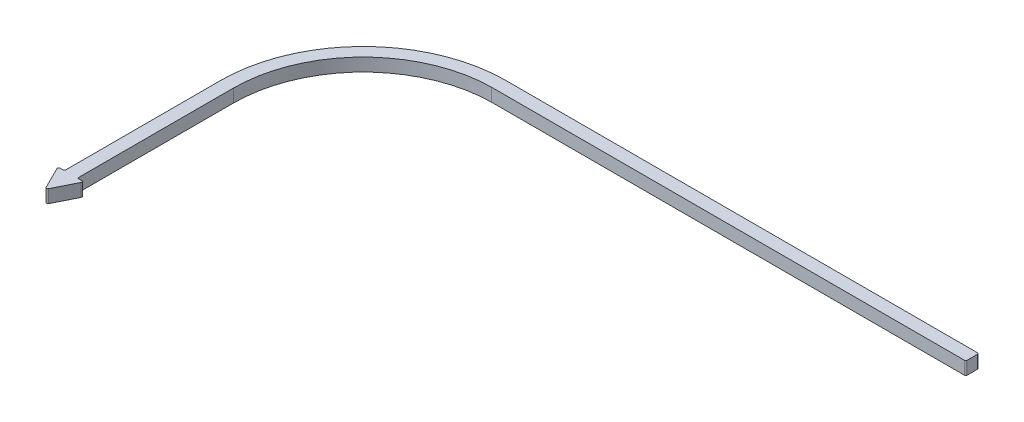
SolidWorks part; units mm, degrees
material "Acrylic (Medium-high impact)"
ref_plane "Front" through (0, 0, 0) normal (0, 0, 1) x (1, 0, 0)
ref_plane "Top" through (0, 0, 0) normal (0, 1, 0) x (1, 0, 0)
ref_plane "Right" through (0, 0, 0) normal (1, 0, 0) x (0, 0, -1)
sketch "Sketch1" plane through (0, 0, 0) normal (0, 1, 0) x (1, 0, 0)
  line L0 (69.0717, 158.7457) -> (69.0717, 152.3952)
  line L1 (0, 0) -> (6.35, 0)
  line L2 (0, 0) -> (0, 88.9)
  line L3 (0, 88.9) -> (6.35, 88.9)
  line L4 (6.35, 0) -> (6.35, 88.9)
  line L9 (69.0717, 158.7457) -> (300.8467, 158.7457)
  line L10 (69.0717, 152.3952) -> (300.8467, 152.3952)
  line L11 (300.8467, 158.7457) -> (300.8467, 152.3952)
  line L19 (9.525, 0) -> (-3.175, 0)
  line L20 (9.525, 0) -> (9.525, 12.7)
  line L21 (9.525, 12.7) -> (-3.175, 12.7)
  line L22 (-3.175, 0) -> (-3.175, 12.7)
  arc A0 (6.35, 88.9) -> (69.0717, 152.3952) centre (69.85, 88.9) cw
  arc A1 (0, 88.9) -> (69.0717, 158.7457) centre (69.85, 88.9) cw
  point P14 (3.175, 0)
  dimension "D1" = 6.35
  dimension "D2" = 88.9
  dimension "D3" = 231.775
  dimension "D4" = 63.5
  dimension "D5" = 12.7
  dimension "D6" = 12.7
  dimension "D7" = 12.7
  dimension "D8" = 6.35
extrude "Boss-Extrude1" add sketch "Sketch1" along normal blind 6.35 contours L1 L4 L3 L2 | A1 L3 A0 L0 | L11 L9 L0 L10 | L20 L19 L22 L21 region at (184.9592, 0, -155.5704) region at (68.0894, 0, -155.5704) region at (3.175, 0, -50.8)
sketch "Sketch2" plane through (0, 6.35, 0) normal (0, 1, 0) x (1, 0, 0)
  line L0 (-3.175, 12.7) -> (3.175, 0)
  line L1 (9.525, 0) -> (-3.175, 0) construction
  line L2 (3.175, 0) -> (9.525, 12.7)
  line L3 (-3.175, 12.7) -> (9.525, 12.7)
  line L4 (9.525, 12.7) -> (9.525, 0)
  line L5 (9.525, 0) -> (-3.175, 0)
  line L6 (-3.175, 0) -> (-3.175, 12.7) construction
  line L7 (-3.175, 0) -> (-3.175, 12.7)
  line M3 (-3.175, 12.7) -> (-3.175, 0)
  line M4 (-3.175, 0) -> (9.525, 0)
  line M5 (9.525, 0) -> (9.525, 12.7)
extrude "Cut-Extrude1" cut sketch "Sketch2" against normal through all contours L0 M3 M4 | L2 M4 M5 region at (-1.0583, 6.35, -4.2333) region at (7.4083, 6.35, -4.2333)
fillet "Fillet1" radius 0.635 7 edges at (300.8467, 3.175, -158.7457) (300.8467, 3.175, -152.3952) (6.35, 3.175, -12.7) (0, 3.175, -12.7) (-3.175, 3.175, -12.7) (9.525, 3.175, -12.7) (3.175, 3.175, 0)
